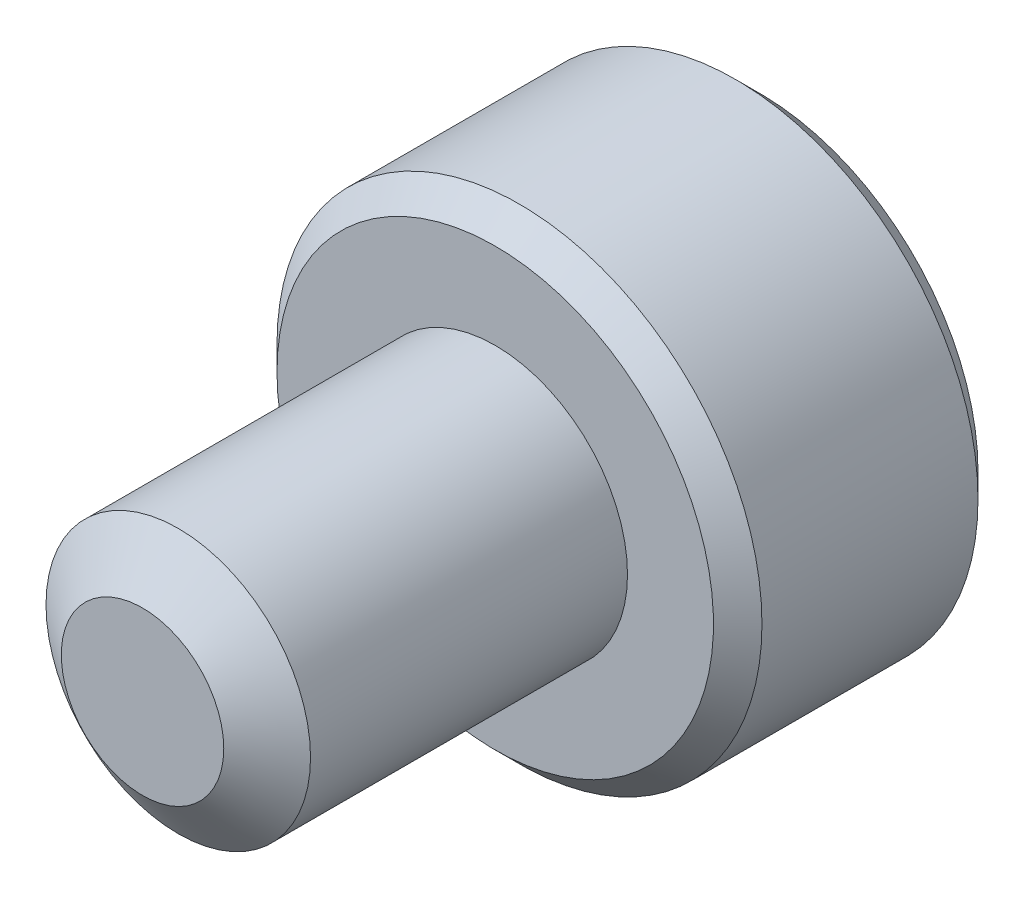
SolidWorks part; units mm, degrees
other "DetailItem1"
material "AISI 304"
ref_plane "Front Plane" through (0, 0, 0) normal (0, 0, 1) x (1, 0, 0)
ref_plane "Top Plane" through (0, 0, 0) normal (0, 1, 0) x (1, 0, 0)
ref_plane "Right Plane" through (0, 0, 0) normal (1, 0, 0) x (0, 0, -1)
sketch "Sketch1" plane through (0, 0, 0) normal (0, 0, 1) x (1, 0, 0)
  circle A0 centre (0, 0) radius 1.5
  dimension "OD" = 3
extrude "Extrude1" add sketch "Sketch1" against normal blind 4
sketch "Sketch2" plane through (0, 0, 0) normal (0, 0, 1) x (1, 0, 0)
  circle A0 centre (0, 0) radius 1.5 construction
  circle A1 centre (0, 0) radius 1.5
curve "Helix/Spiral1" [suppressed] pitch 0.5 height 4.5 turns 9 parameters "pitch"=0.5
sketch "Sketch3" plane through (0, 0, 0) normal (1, 0, 0) x (0, 0, -1)
  line L0 (-0.4375, 1.5) -> (-0.25, 1.1752)
  line L1 (-0.25, 1.1752) -> (-0.1875, 1.1752)
  line L2 (-0.1875, 1.1752) -> (0, 1.5)
  line L3 (-0.4375, 1.5) -> (0, 1.5)
  line L4 (-0.2187, 1.5) -> (-0.2188, 1.1752) construction
  line L5 (-0.3438, 1.3376) -> (-0.0938, 1.3376) construction
  line L6 (0, 1.5) -> (0, -1.5) construction
  dimension "D1" = 0.0625
  dimension "D2" = 0.25
  dimension "D3" = 60
sweep "Cut-Sweep1" [suppressed] cut profiles "Sketch3" path "Helix/Spiral1"
sketch "Sketch4" plane through (0, 0, 0) normal (1, 0, 0) x (0, 0, -1)
  line L0 (0.4053, 1.5) -> (0, 0.9212)
  line L1 (0, 0.9212) -> (0, 1.5)
  line L2 (0.4053, 1.5) -> (0, 1.5)
  line L3 (-0.4375, 1.5) -> (0, 1.5) construction
  line L4 (0, 0) -> (7.0209, 0) construction
  dimension "D1" = 55
  dimension "D2" = 0.254
revolve "Cut-Revolve1" cut sketch "Sketch4" angle 360 about L4
sketch "Sketch6" plane through (0, 0, -4) normal (0, 0, -1) x (-1, 0, 0)
  circle A0 centre (0, 0) radius 2.75
  dimension "head dia" = 5.5
extrude "Extrude2" add sketch "Sketch6" along normal blind 3
sketch "Sketch7" plane through (0, 0, -7) normal (0, 0, -1) x (-1, 0, 0)
  line L1 (0, 1.4434) -> (-1.25, 0.7217)
  line L2 (-1.25, 0.7217) -> (-1.25, -0.7217)
  line L3 (-1.25, -0.7217) -> (0, -1.4434)
  line L4 (0, -1.4434) -> (1.25, -0.7217)
  line L5 (1.25, -0.7217) -> (1.25, 0.7217)
  line L6 (1.25, 0.7217) -> (0, 1.4434)
  circle A0 centre (0, 0) radius 1.25 construction
  dimension "hex dia" = 2.5
extrude "Cut-Extrude1" cut sketch "Sketch7" against normal blind 1.875
sketch "Sketch8" plane through (0, 0, -7) normal (0, 0, -1) x (-1, 0, 0)
  circle A0 centre (0, 0) radius 1.4434
extrude "Cut-Extrude2" cut sketch "Sketch8" against normal through all draft 45
chamfer "Chamfer1" distance 0.275 angle 45 2 edges at (-2.75, 0, -7) (-2.75, 0, -4)
sketch "Sketch10" plane through (0, 0, -4) normal (0, 0, 1) x (1, 0, 0)
  circle A1 centre (0, 0) radius 1.5
  circle A2 centre (0, 0) radius 1.5
  dimension "D1" = 0
ref_plane "Plane1" through (0, 0, 0) normal (0, 0, 1) x (1, 0, 0)
extrude "partial thread" [suppressed] add sketch "Sketch10" along normal up to surface (4 mm away) separate body up to plane "Plane1"
chamfer "Chamfer2" [suppressed] distance 0.06 angle 45
combine bodies "Combine1" [suppressed] operation type add bodies to combine 107 108
sketch "Sketch9" plane through (0, 0, 0) normal (1, 0, 0) x (0, 0, -1)
  line L0 (0, 1.5) -> (0, -1.5) construction
  line L1 (1.25, 1.5) -> (1.25, -1.5) construction
  dimension "D1" = 1.25
equation "\"D3@Helix/Spiral1\" = \"screw length@Extrude1\"+\"pitch@Helix/Spiral1\""
equation "\"D1@Sketch3\" = \"pitch@Helix/Spiral1\"*.125"
equation "\"D2@Sketch3\" = \"pitch@Helix/Spiral1\"*.5"
equation "\"D1@Cut-Extrude1\" = \"hex dia@Sketch7\"*.75"
equation "\"D1@Chamfer1\" = \"head dia@Sketch6\"*.05"
equation "\"D1@Sketch9\" = \"pitch@Helix/Spiral1\"*2.5"
equation "\"D1@Chamfer2\"=\"OD@Sketch1\"*.02"
